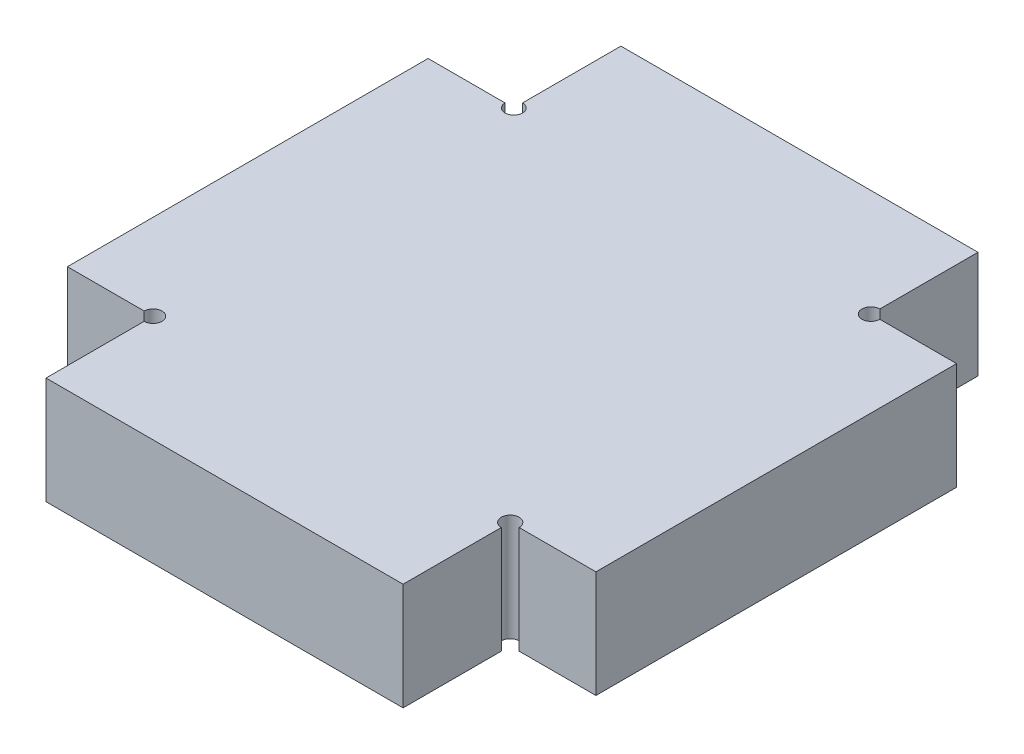
SolidWorks part; units mm, degrees
ref_plane "Front Plane" through (0, 0, 0) normal (0, 0, 1) x (1, 0, 0)
ref_plane "Top Plane" through (0, 0, 0) normal (0, 1, 0) x (1, 0, 0)
ref_plane "Right Plane" through (0, 0, 0) normal (1, 0, 0) x (0, 0, -1)
sketch "Sketch1" plane through (0, 0, 0) normal (0, 1, 0) x (1, 0, 0)
  line L0 (0.25, 5.3321) -> (2.4, 5.3321)
  line L1 (2.4, 5.3321) -> (2.4, -4.7679)
  line L2 (2.4, -4.7679) -> (0.25, -4.7679)
  line L3 (0, -5.0179) -> (0, -7.7679)
  line L4 (0, -7.7679) -> (-10, -7.7679)
  line L5 (0, 5.5821) -> (0, 8.3321)
  line L6 (0, 8.3321) -> (-10, 8.3321)
  line L7 (-10, 8.3321) -> (-10, 5.5774)
  line L8 (-10.2453, 5.3321) -> (-12.4, 5.3321)
  line L9 (-10, -7.7679) -> (-10, -5.0179)
  line L10 (-10.25, -4.7679) -> (-12.4, -4.7679)
  line L11 (-12.4, -4.7679) -> (-12.4, 5.3321)
  arc A0 (-10.2453, 5.3321) -> (-10, 5.5774) centre (-10, 5.3321) ccw
  arc A1 (-10, -5.0179) -> (-10.25, -4.7679) centre (-10, -4.7679) ccw
  arc A2 (0.25, -4.7679) -> (0, -5.0179) centre (0, -4.7679) ccw
  arc A3 (0, 5.5821) -> (0.25, 5.3321) centre (0, 5.3321) ccw
  dimension "D1" = 10.1
  dimension "D2" = 2.4
  dimension "D3" = 3
  dimension "D4" = 3
  dimension "D5" = 10
  dimension "D6" = 10
  dimension "D7" = 2.4
extrude "Boss-Extrude1" add sketch "Sketch1" along normal blind 3
